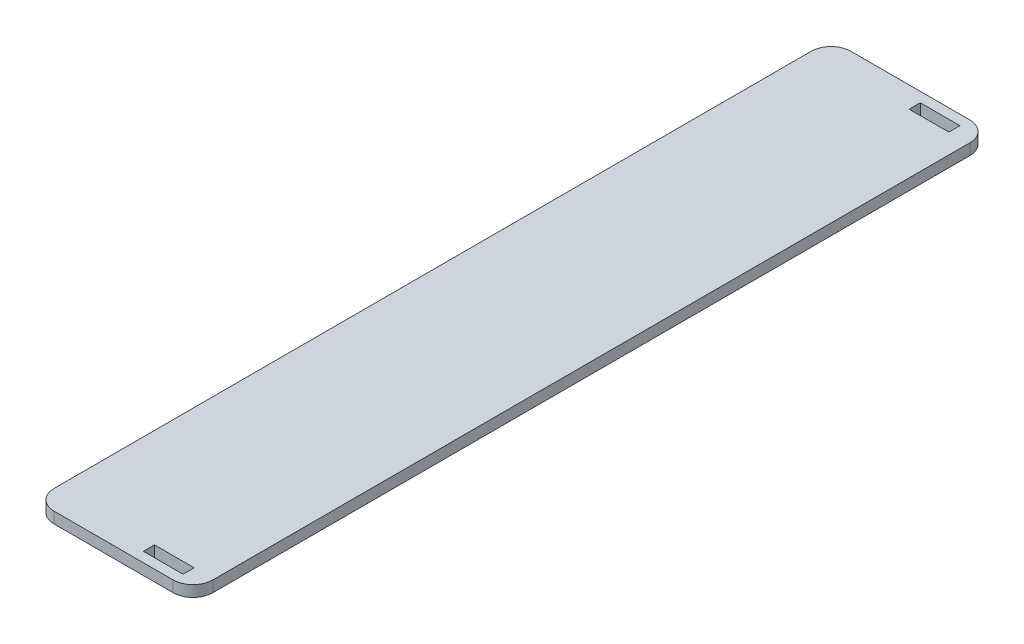
SolidWorks part; units mm, degrees
material "t5ハニカムプラダン"
ref_plane "正面" through (0, 0, 0) normal (0, 0, 1) x (1, 0, 0)
ref_plane "平面" through (0, 0, 0) normal (0, 1, 0) x (1, 0, 0)
ref_plane "右側面" through (0, 0, 0) normal (1, 0, 0) x (0, 0, -1)
sketch "ｽｹｯﾁ1" plane through (0, 0, 0) normal (0, 1, 0) x (1, 0, 0)
  line L0 (0, -200.9) -> (0, 0) construction
  line L1 (-20, 200.9) -> (20, 200.9)
  line L2 (-20, 200.9) -> (-20, -200.9) construction
  line L3 (-20, -200.9) -> (20, -200.9)
  line L4 (20, 200.9) -> (20, -200.9)
  line L5 (-20, 200.9) -> (20, -200.9) construction
  line L6 (-20, -200.9) -> (20, 200.9) construction
  line L7 (0, 0) -> (20, 0) construction
  line L8 (-10, 195.9) -> (10, 190.3) construction
  line L9 (-10, -190.3) -> (10, -190.3)
  line L10 (-10, -190.3) -> (-10, -195.9)
  line L11 (-10, -195.9) -> (10, -195.9)
  line L12 (10, -190.3) -> (10, -195.9)
  line L13 (-10, -190.3) -> (10, -195.9) construction
  line L14 (-10, -195.9) -> (10, -190.3) construction
  line L15 (-10, 190.3) -> (10, 195.9) construction
  line L16 (10, 190.3) -> (10, 195.9)
  line L17 (-10, 195.9) -> (10, 195.9)
  line L18 (-10, 190.3) -> (-10, 195.9)
  line L19 (-10, 190.3) -> (10, 190.3)
  line L21 (-20, -200.9) -> (-60, -200.9)
  line L22 (-20, -200.9) -> (-20, 200.9) construction
  line L23 (-20, 200.9) -> (-60, 200.9)
  line L24 (-60, -200.9) -> (-60, 200.9)
  point P0 (0, 0)
  point P9 (0, -193.1)
  point P18 (0, 193.1)
  dimension "D1" = 401.8
  dimension "D2" = 40
  dimension "D3" = 20
  dimension "D4" = 5.6
  dimension "D5" = 5
  dimension "D6" = 50
extrude "ﾎﾞｽ - 押し出し1" add sketch "ｽｹｯﾁ1" along normal blind 5.6
fillet "ﾌｨﾚｯﾄ1" radius 10 4 edges at (20, 2.8, -200.9) (20, 2.8, 200.9) (-60, 2.8, -200.9) (-60, 2.8, 200.9)
